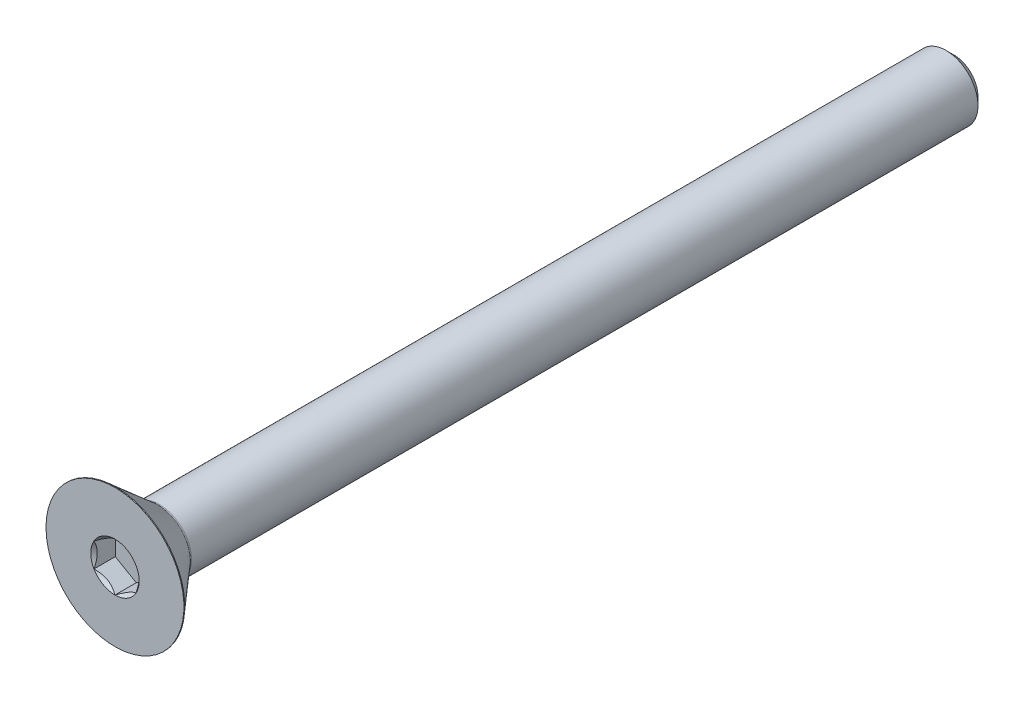
SolidWorks part; units mm, degrees
ref_plane "Front Plane" through (0, 0, 0) normal (0, 0, 1) x (1, 0, 0)
ref_plane "Top Plane" through (0, 0, 0) normal (0, 1, 0) x (1, 0, 0)
ref_plane "Right Plane" through (0, 0, 0) normal (1, 0, 0) x (0, 0, -1)
sketch "Sketch1" plane through (0, 0, 0) normal (1, 0, 0) x (0, 0, -1)
  line L0 (-31.75, 0) -> (31.75, 0) construction
  line L1 (-31.75, 0) -> (-31.75, 5.2197)
  line L2 (-31.75, 5.2197) -> (-31.6855, 5.2197)
  line L3 (-31.6855, 5.2197) -> (-28.5242, 2.4716)
  line L4 (-31.6855, -5.2197) -> (-28.5242, -2.4716)
  line L5 (31.75, 0) -> (31.75, 2.413)
  line L6 (31.75, 2.413) -> (-28.5242, 2.413)
  line L7 (31.1547, 2.413) -> (31.75, 1.8177)
  line L8 (31.7004, 2.4989) -> (32.0973, 1.8115) construction
  line L9 (32.0973, 1.8115) -> (32.4941, 2.4989) construction
  line L10 (32.4941, 2.4989) -> (31.7004, 2.4989) construction
  line L11 (31.7252, 2.456) -> (32.4693, 2.456)
  line L12 (32.4693, 2.456) -> (32.1469, 1.8974)
  line L13 (32.1469, 1.8974) -> (32.0477, 1.8974)
  line L14 (32.0477, 1.8974) -> (31.7252, 2.456)
  line L15 (32.0973, 1.8974) -> (32.0973, 1.8115) construction
  line L16 (31.75, 2.413) -> (32.4445, 2.413) construction
  line L17 (32.0973, 2.4989) -> (32.0973, 2.413) construction
  line L18 (31.75, -2.413) -> (-28.5242, -2.413)
  arc A0 (-28.5242, 2.4716) -> (-28.3674, 2.413) centre (-28.3674, 2.6521) ccw
  point P2 (0, 0)
  point P23 (-30.1371, 0)
  point P27 (32.0973, 2.456)
  point P30 (30.5594, -2.413)
  point P31 (-25.7575, 2.413)
  point P32 (29.1401, 2.413)
  point P33 (-28.5242, 5.2197)
  point P34 (-31.6855, -5.2197)
  point P37 (-25.1051, 2.413)
  dimension "Length" = 63.5
  dimension "Head Height" = 3.2258
  dimension "Head Diameter" = 10.4394
  dimension "Countersink Angle" = 82
  dimension "Screw Size Decimal Equivalent" = 4.826
  dimension "Pitch" = 0.7937
  dimension "D4" = 0.0992
  dimension "D3" = 45
  dimension "D5" = 0.5953
  dimension "D6" = 1.6129
  dimension "D1" = 1.1906
  dimension "D7" = 2.6098
  dimension "D8" = 2.6098
  dimension "D9" = 3.2623
  dimension "D2" = 0.0645
sketch "Sketch8" plane through (0, 0, 0) normal (0, 0, 1) x (1, 0, 0)
  line L1 (0, 1.8331) -> (-1.5875, 0.9165)
  line L2 (-1.5875, 0.9165) -> (-1.5875, -0.9165)
  line L3 (-1.5875, -0.9165) -> (0, -1.8331)
  line L4 (0, -1.8331) -> (1.5875, -0.9165)
  line L5 (1.5875, -0.9165) -> (1.5875, 0.9165)
  line L6 (1.5875, 0.9165) -> (0, 1.8331)
  circle A0 centre (0, 0) radius 1.5875 construction
  dimension "Drive Size" = 3.175
sketch "Sketch2" plane through (0, 0, 0) normal (1, 0, 0) x (0, 0, -1)
  line L0 (-31.6855, 5.2197) -> (-28.5242, 2.4716) construction
  line L1 (-31.75, 0) -> (-31.75, 5.2197) construction
  line L2 (-31.6855, 5.2197) -> (-28.5242, 2.4716)
  line L3 (-31.75, 0) -> (-31.75, 5.2197)
  line L4 (-31.75, 5.2197) -> (-31.6855, 5.2197) construction
  line L5 (-31.75, 5.2197) -> (-31.6855, 5.2197)
  line L6 (-28.3674, 2.413) -> (31.1547, 2.413)
  line L7 (31.1547, 2.413) -> (31.75, 1.8177)
  line L8 (31.75, 1.8177) -> (31.75, 0)
  line L9 (31.75, 0) -> (-31.75, 0)
  arc A0 (-28.5242, 2.4716) -> (-28.3674, 2.413) centre (-28.3674, 2.6521) ccw construction
  arc A1 (-28.5242, 2.4716) -> (-28.3674, 2.413) centre (-28.3674, 2.6521) ccw
revolve "Revolve1" add sketch "Sketch2" angle 360 about L9
sketch "Sketch9" plane through (0, 0, 31.75) normal (0, 0, 1) x (1, 0, 0)
  line L0 (1.5875, -0.9165) -> (1.5875, 0.9165) construction
  line L1 (0, -1.8331) -> (1.5875, -0.9165) construction
  line L2 (-1.5875, -0.9165) -> (0, -1.8331) construction
  line L3 (-1.5875, 0.9165) -> (-1.5875, -0.9165) construction
  line L4 (0, 1.8331) -> (-1.5875, 0.9165) construction
  line L5 (1.5875, 0.9165) -> (0, 1.8331) construction
  line L6 (1.5875, -0.9165) -> (1.5875, 0.9165)
  line L7 (0, -1.8331) -> (1.5875, -0.9165)
  line L8 (-1.5875, -0.9165) -> (0, -1.8331)
  line L9 (-1.5875, 0.9165) -> (-1.5875, -0.9165)
  line L10 (0, 1.8331) -> (-1.5875, 0.9165)
  line L11 (1.5875, 0.9165) -> (0, 1.8331)
sketch "Sketch10" plane through (0, 0, 31.75) normal (0, 0, 1) x (1, 0, 0)
  circle A0 centre (0, 0) radius 1.8331
extrude "Cut-Extrude2" cut sketch "Sketch10" against normal up to vertex (1.6129 mm away) draft 45 up to point (0, 0, 30.1371)
extrude "Cut-Extrude1" cut sketch "Sketch9" against normal up to vertex (1.6129 mm away) up to point (0, 0, 30.1371)
ref_plane "Plane1" [suppressed] through (0, 0, 28.3674) normal (0, 0, 1) x (1, 0, 0)
split "Split1" [suppressed] bodies to split 111
sketch "Sketch3" [suppressed] plane through (0, 0, -31.75) normal (0, 0, -1) x (-1, 0, 0)
  circle A0 centre (0, 0) radius 2.413 construction
  circle A1 centre (0, 0) radius 2.413
curve "Helix/Spiral1" [suppressed] pitch 0.7937 height 63.5 turns 80
sketch "Sketch4" [suppressed] plane through (0, 0, 0) normal (1, 0, 0) x (0, 0, -1)
  line L0 (31.7252, 2.456) -> (32.4693, 2.456) construction
  line L1 (32.0477, 1.8974) -> (31.7252, 2.456) construction
  line L2 (32.1469, 1.8974) -> (32.0477, 1.8974) construction
  line L3 (32.4693, 2.456) -> (32.1469, 1.8974) construction
  line L4 (31.7252, 2.456) -> (32.4693, 2.456)
  line L5 (32.0477, 1.8974) -> (31.7252, 2.456)
  line L6 (32.1469, 1.8974) -> (32.0477, 1.8974)
  line L7 (32.4693, 2.456) -> (32.1469, 1.8974)
sweep "Cut-Sweep1" [suppressed] cut profiles "Sketch4" path "Helix/Spiral1"
sketch "Sketch7" [suppressed] plane through (0, 0, 28.3674) normal (0, 0, 1) x (1, 0, 0)
  circle A0 centre (0, 0) radius 2.413
extrude "Boss-Extrude2" [suppressed] add sketch "Sketch7" against normal up to next draft 20
equation "\"D4@Sketch1\" = \"Pitch@Sketch1\" / 8"
equation "\"D5@Sketch1\"=\"Pitch@Sketch1\"*0.75"
equation "\"D4@Helix/Spiral1\"=\"Pitch@Sketch1\""
equation "\"D3@Helix/Spiral1\"=\"Length@Sketch1\""
equation "\"D6@Sketch1\"=\"Head Height@Sketch1\"/2"
equation "\"D1@Sketch1\"=\"Pitch@Sketch1\"*1.5"
equation "\"D7@Sketch1\"=\"Head Diameter@Sketch1\"*0.25"
equation "\"D8@Sketch1\"=\"D7@Sketch1\""
equation "\"D9@Sketch1\"=1.25*\"D7@Sketch1\""
